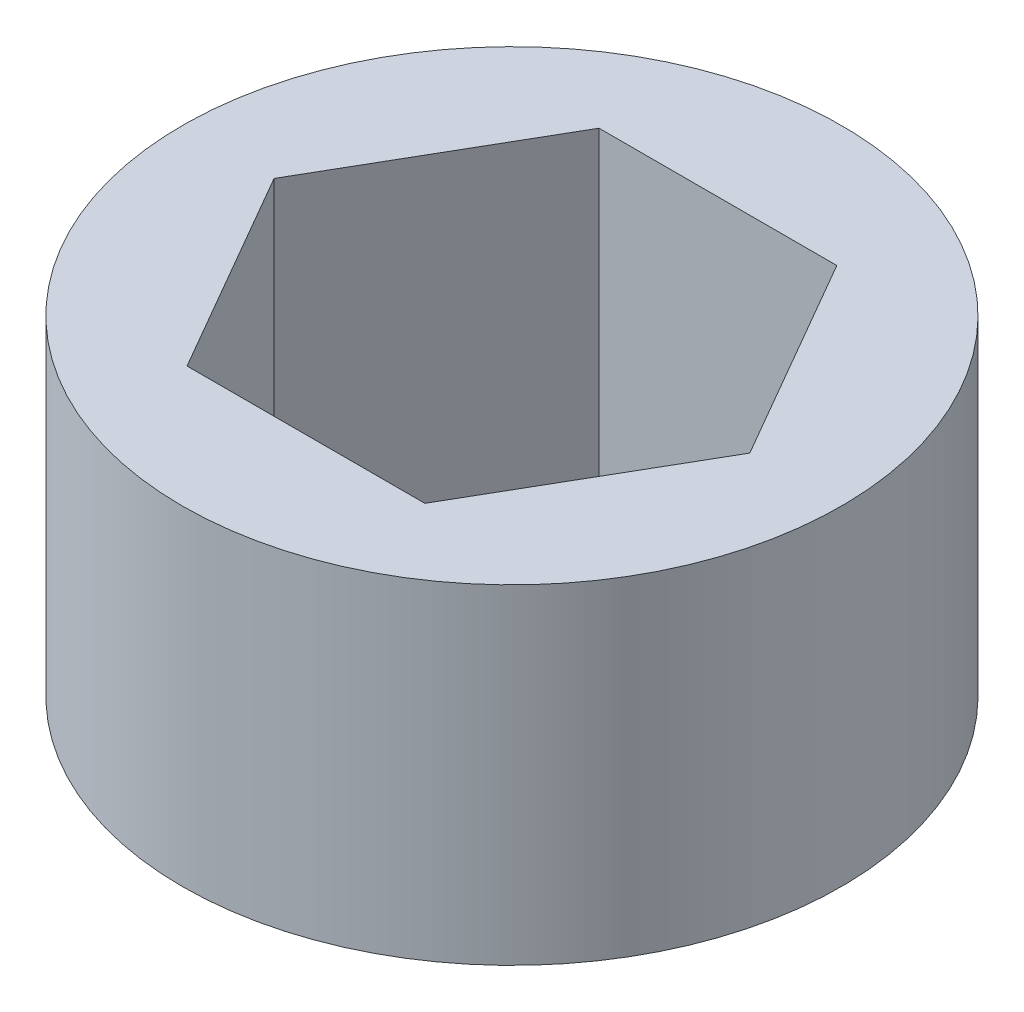
SolidWorks part; units mm, degrees
ref_plane "Front" through (0, 0, 0) normal (0, 0, 1) x (1, 0, 0)
ref_plane "Top" through (0, 0, 0) normal (0, 1, 0) x (1, 0, 0)
ref_plane "Right" through (0, 0, 0) normal (1, 0, 0) x (0, 0, -1)
sketch "Sketch1" plane through (0, 0, 0) normal (0, 1, 0) x (1, 0, 0)
  line L1 (2.8868, 0) -> (1.4434, 2.5)
  line L2 (1.4434, 2.5) -> (-1.4434, 2.5)
  line L3 (-1.4434, 2.5) -> (-2.8868, 0)
  line L4 (-2.8868, 0) -> (-1.4434, -2.5)
  line L5 (-1.4434, -2.5) -> (1.4434, -2.5)
  line L6 (1.4434, -2.5) -> (2.8868, 0)
  circle A0 centre (0, 0) radius 2.5 construction
  circle A1 centre (0, 0) radius 4
extrude "Boss-Extrude1" add sketch "Sketch1" along normal blind 4
